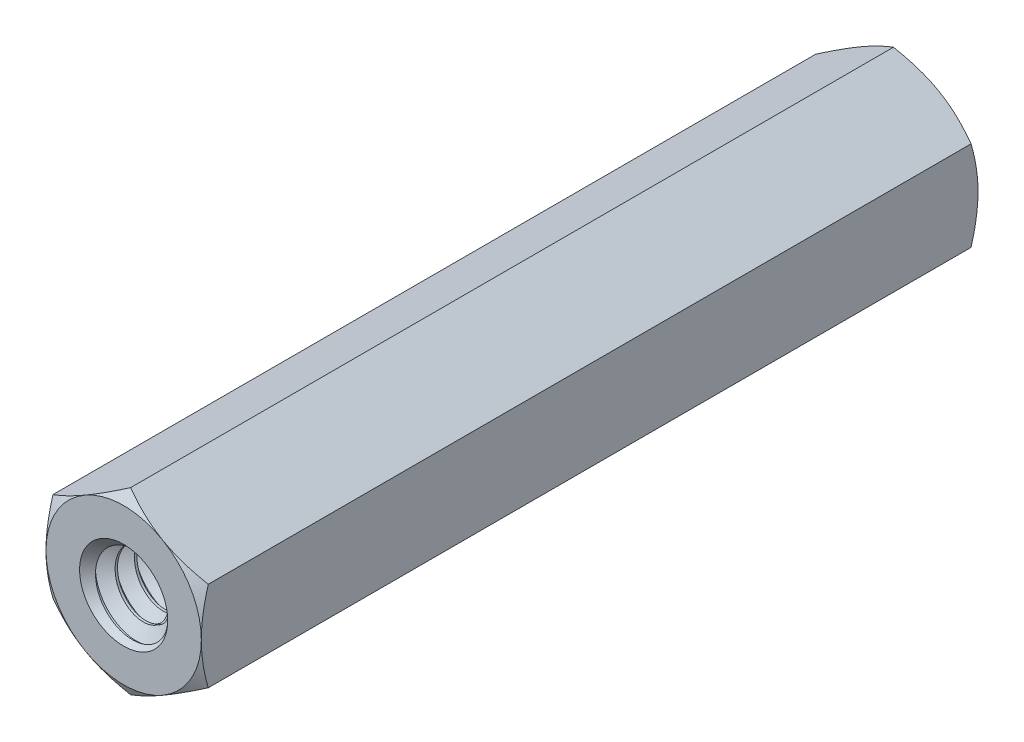
SolidWorks part; units mm, degrees
ref_plane "Front Plane" through (0, 0, 0) normal (0, 0, 1) x (1, 0, 0)
ref_plane "Top Plane" through (0, 0, 0) normal (0, 1, 0) x (1, 0, 0)
ref_plane "Right Plane" through (0, 0, 0) normal (1, 0, 0) x (0, 0, -1)
sketch "Sketch3" plane through (0, 0, 0) normal (1, 0, 0) x (0, 0, -1)
  line L0 (-15.875, 0) -> (15.875, 0) construction
  line L1 (0, 3.175) -> (0, -3.175) construction
  line L2 (-15.875, 1.7526) -> (-15.875, -1.7526) construction
  point P2 (6.35, 0)
  point P3 (-6.35, 0)
  dimension "D1" = 9.525
  dimension "Length" = 31.75
  dimension "Min Thread Length" = 9.525
  dimension "Thread Dia" = 3.5052
  dimension "Hex" = 6.35
sketch "Sketch1" plane through (0, 0, 0) normal (0, 0, 1) x (1, 0, 0)
  line L1 (0, 3.6662) -> (-3.175, 1.8331)
  line L2 (-3.175, 1.8331) -> (-3.175, -1.8331)
  line L3 (-3.175, -1.8331) -> (0, -3.6662)
  line L4 (0, -3.6662) -> (3.175, -1.8331)
  line L5 (3.175, -1.8331) -> (3.175, 1.8331)
  line L6 (3.175, 1.8331) -> (0, 3.6662)
  circle A0 centre (0, 0) radius 3.175 construction
  circle A1 centre (0, 0) radius 1.7526
extrude "Extrude1" add sketch "Sketch1" along normal up to vertex (15.875 mm away) and the other way up to vertex (15.875 mm away) up to point (0, 0, 15.875) other way up to point (0, 0, -15.875)
sketch "Sketch11" plane through (0, 0, -15.875) normal (0, 0, -1) x (-1, 0, 0)
  circle A0 centre (0, 0) radius 1.7526 construction
  circle A1 centre (0, 0) radius 1.7526
curve "Helix/Spiral1" pitch 0.7937 height 32.5437 radius 1.7526 centre (0, 0, -15.875) axis (0, 0, 1) start towards (0, 1, 0) parameters "Pitch"=0.7937
sketch "Sketch12" plane through (0, 0, 0) normal (1, 0, 0) x (0, 0, -1)
  line L0 (16.5695, 1.7526) -> (15.875, 1.7526)
  line L1 (16.5695, 1.7526) -> (16.2719, 1.237)
  line L2 (16.2719, 1.237) -> (16.1727, 1.237)
  line L3 (16.1727, 1.237) -> (15.875, 1.7526)
  line L4 (16.2223, 1.237) -> (16.2223, 1.7526) construction
  line L5 (16.4207, 1.4948) -> (16.0238, 1.4948) construction
  dimension "D1" = 0.0992
  dimension "D2" = 0.3969
  dimension "D3" = 60
sweep "Sweep1" add profiles "Sketch12" path "Helix/Spiral1"
sketch "Sketch6" plane through (0, 0, -15.875) normal (0, 0, -1) x (-1, 0, 0)
  line L6 (0, 3.6662) -> (-3.175, 1.8331)
  line L7 (-3.175, 1.8331) -> (-3.175, -1.8331)
  line L8 (-3.175, -1.8331) -> (0, -3.6662)
  line L9 (0, -3.6662) -> (3.175, -1.8331)
  line L10 (3.175, -1.8331) -> (3.175, 1.8331)
  line L11 (3.175, 1.8331) -> (0, 3.6662)
  line L12 (0, 3.6662) -> (-3.175, 1.8331)
  line L13 (-3.175, 1.8331) -> (-3.175, -1.8331)
  line L14 (-3.175, -1.8331) -> (0, -3.6662)
  line L15 (0, -3.6662) -> (3.175, -1.8331)
  line L16 (3.175, -1.8331) -> (3.175, 1.8331)
  line L17 (3.175, 1.8331) -> (0, 3.6662)
  dimension "D1" = 0
extrude "Extrude2" cut sketch "Sketch6" along normal through all
sketch "Sketch7" plane through (0, 0, -15.875) normal (0, 0, -1) x (-1, 0, 0)
  circle A2 centre (0, 0) radius 1.8034
  circle A3 centre (0, 0) radius 1.8034
  dimension "D1" = 0.0508
extrude "Extrude3" cut sketch "Sketch7" against normal through all draft 43
sketch "Sketch8" plane through (0, 0, -15.875) normal (0, 0, -1) x (-1, 0, 0)
  circle A0 centre (0, 0) radius 3.175 construction
  circle A1 centre (0, 0) radius 3.175
extrude "Extrude4" cut sketch "Sketch8" against normal through all draft 60 flip side to cut
mirror "Mirror1" about plane through (0, 0, 0) normal (0, 0, 1) of "Extrude2", "Extrude3", "Extrude4"
sketch "Sketch9" plane through (0, 0, 0) normal (1, 0, 0) x (0, 0, -1)
  line L1 (-6.35, 1.8034) -> (6.35, 1.8034)
  line L2 (-6.35, 1.8034) -> (-6.35, 0)
  line L3 (-6.35, 0) -> (6.35, 0)
  line L4 (6.35, 1.8034) -> (6.35, 0)
  line L7 (-15.875, 0) -> (15.875, 0) construction
revolve "Revolve" add sketch "Sketch9" angle 360 about L0
sketch "Sketch10" plane through (0, 0, 0) normal (1, 0, 0) x (0, 0, -1)
  line L0 (15.875, 1.7526) -> (6.35, 1.7526)
  line L1 (-15.875, 1.7526) -> (-6.35, 1.7526)
  line L2 (6.35, 1.7526) -> (6.35, -1.7526)
  line L3 (-15.875, -1.8034) -> (-6.35, -1.8034)
  line L4 (-6.35, 1.7526) -> (-6.35, -1.8034)
  line L5 (6.35, -1.7526) -> (15.875, -1.7526)
equation "\"D1@Sketch3\" = \"Min Thread Length@Sketch3\""
equation "\"D3@Helix/Spiral1\" = \"Length@Sketch3\"+\"Pitch@Helix/Spiral1\""
equation "\"D1@Sketch12\" = \"Pitch@Helix/Spiral1\"*.125"
equation "\"D2@Sketch12\" = \"Pitch@Helix/Spiral1\"*.5"
